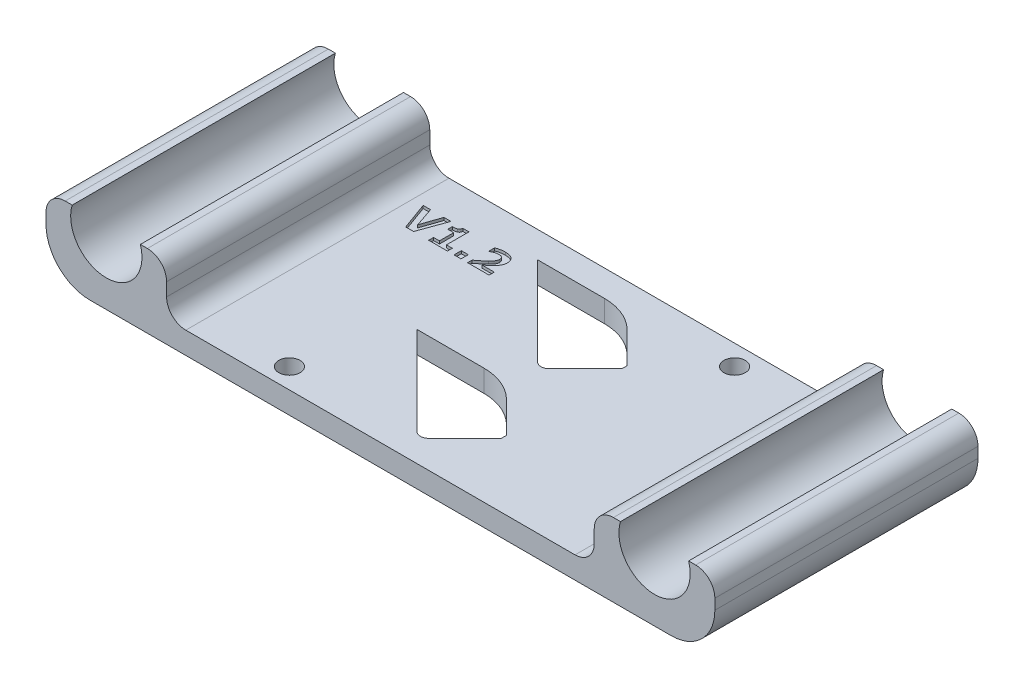
SolidWorks part; units mm, degrees
ref_plane "Front Plane" through (0, 0, 0) normal (0, 0, 1) x (1, 0, 0)
ref_plane "Top Plane" through (0, 0, 0) normal (0, 1, 0) x (1, 0, 0)
ref_plane "Right Plane" through (0, 0, 0) normal (1, 0, 0) x (0, 0, -1)
sketch "Sketch1" plane through (0, 0, 0) normal (0, 0, 1) x (1, 0, 0)
  line L0 (0, 13.4) -> (4.7839, 13.4)
  line L1 (0, 13.4) -> (0, 0)
  line L2 (122, 13.4) -> (122, 0)
  line L4 (117.2161, 13.4) -> (122, 13.4)
  line L5 (100, 13.4) -> (100, 4)
  line L6 (22, 4) -> (22, 13.4)
  line L7 (22, 4) -> (100, 4)
  line L8 (17.2161, 13.4) -> (22, 13.4)
  line L9 (11, 13.4) -> (11, 11.5) construction
  line L10 (11, 11.5) -> (111, 11.5) construction
  line L13 (100, 13.4) -> (104.7839, 13.4)
  line L18 (0, 0) -> (122, 0)
  arc A0 (104.7839, 13.4) -> (117.2161, 13.4) centre (111, 11.5) ccw
  arc A1 (4.7839, 13.4) -> (17.2161, 13.4) centre (11, 11.5) ccw
  dimension "D6" = 6.5
  dimension "D5" = 22
  dimension "D1" = 7.5
  dimension "D2" = 4
  dimension "D3" = 100
  dimension "D4" = 22
  dimension "D7" = 1.9
  dimension "D8" = 11
extrude "Boss-Extrude1" add sketch "Sketch1" along normal blind 48
fillet "Fillet1" radius 3.5 6 edges at (0, 13.4, 24) (22, 4, 24) (22, 13.4, 24) (100, 4, 24) (100, 13.4, 24) (122, 13.4, 24)
fillet "Fillet2" radius 8 2 edges at (122, 0, 24) (0, 0, 24)
ref_plane "Plane1" through (0, 0, 24) normal (0, 0, -1) x (-1, 0, 0)
ref_plane "Plane2" through (61, 0, 0) normal (-1, 0, 0) x (0, 0, 1)
sketch "Sketch6" plane through (0, 0, 0) normal (0, -1, 0) x (1, 0, 0)
  circle A0 centre (40.7, 44.3) radius 1.95
  circle A1 centre (81.3, 3.7) radius 1.95
  point P0 (40.7, 44.3)
  point P1 (81.3, 3.7)
  dimension "D1" = 3.9
extrude "Cut-Extrude2" cut sketch "Sketch6" against normal blind 6
sketch "Sketch7" plane through (0, 0, 0) normal (0, -1, 0) x (1, 0, 0)
  line L0 (63.6751, 44) -> (46.477, 26.8018)
  line L1 (71.3683, 36.3068) -> (63.6751, 44)
  line L2 (62.8027, 26.8018) -> (71.3683, 35.3675)
  line L3 (71.3683, 35.3675) -> (71.3683, 36.3068)
  line L4 (46.477, 26.8018) -> (62.8027, 26.8018)
  line L7 (8, 48) -> (114, 48) construction
  dimension "D1" = 45
  dimension "D2" = 45
  dimension "D3" = 90
  dimension "D4" = 4
extrude "Cut-Extrude3" cut sketch "Sketch7" against normal through all
pattern_linear "LPattern1" count 2 spacing 22 along (0, 0, -1) of "Cut-Extrude3"
fillet "Fillet3" radius 10 2 edges at (62.8027, 2, 26.8018) (62.8027, 2, 4.8018)
sketch "Sketch8" plane through (0, 0, 0) normal (1, 0, 0) x (0, 0, -1)
  line L5 (0, 0) -> (-48, 0) construction
  line L8 (-24, 0) -> (-24, -16.902) construction
  line L9 (-24, -22.0879) -> (-24, 22.0879) construction
  line L10 (-9.75, -0.25) -> (-13.5, -0.25)
  line L11 (-9.75, -3.05) -> (-13.5, -3.05)
  line L12 (-13.5, -5) -> (-8.9588, -5)
  line L13 (-13.5, -0.25) -> (-13.5, 0)
  line L14 (-13.5, 0) -> (-3, 0)
  line L15 (-13.5, -5) -> (-13.5, -3.05)
  line L16 (-3, 0) -> (-8.9588, -5)
  arc A1 (-9.75, -0.25) -> (-9.75, -3.05) centre (-9.75, -1.65) cw
  point P0 (0, 0)
  dimension "D4" = 3
  dimension "D1" = 1.4
  dimension "D2" = 0.25
  dimension "D3" = 40
  dimension "D5" = 3.75
  dimension "D6" = 5
  dimension "D7" = 10.5
extrude "Boss-Extrude2" add sketch "Sketch8" along normal blind 12 from offset 20
fillet "Fillet4" radius 3 2 edges at (26, -5, 8.9588) (26, 0, 3)
fillet "Fillet5" radius 0.5 2 edges at (26, -3.05, 13.5) (26, -5, 13.5)
pattern_linear "LPattern2" count 3 spacing 12 along (0, 0, 1) of "Boss-Extrude2", "Fillet4", "Fillet5"
sketch "Sketch9" plane through (0, 0, 0) normal (0, 0, -1) x (-1, 0, 0)
  line L0 (-32, 0) -> (-29.5, -5)
  line L1 (-8, 0) -> (-114, 0) construction
  line L2 (-29.5, -5) -> (-32, -5)
  line L3 (-32, -5) -> (-32, 0)
  line L4 (-20, 0) -> (-22.5, -5)
  line L5 (-22.5, -5) -> (-20, -5)
  line L6 (-20, -5) -> (-20, 0)
  line L7 (-20, -5) -> (-32, -5) construction
  line L8 (-20, -4.2981) -> (-20, -0.7019) construction
  line L9 (-32, -4.2981) -> (-32, -0.7019) construction
  dimension "D1" = 2.5
  dimension "D2" = 2.5
extrude "Cut-Extrude4" cut sketch "Sketch9" against normal through all
sketch "Sketch10" plane through (0, 4, 0) normal (0, 1, 0) x (1, 0, 0)
  text T0 "V1.2" font "Verdana" height 5
extrude "Cut-Extrude5" cut sketch "Sketch10" against normal blind 0.5
sketch "Sketch11" plane through (0, 0, 0) normal (0, -1, 0) x (1, 0, 0)
  line L1 (38.7, 40.3) -> (42.7, 40.3)
  line L2 (38.7, 40.3) -> (38.7, 5.3)
  line L3 (38.7, 5.3) -> (42.7, 5.3)
  line L4 (42.7, 40.3) -> (42.7, 5.3)
  line L5 (78.3, 4.7) -> (73.3, 4.7)
  line L6 (78.3, 4.7) -> (78.3, 22.7)
  line L7 (78.3, 22.7) -> (73.3, 22.7)
  line L8 (73.3, 4.7) -> (73.3, 22.7)
  line L9 (40.7, 40.3) -> (40.7, 44.3) construction
  point P12 (81.3, 3.7)
  dimension "D1" = 4
  dimension "D2" = 35
  dimension "D3" = 4
  dimension "D4" = 1
  dimension "D5" = 18
  dimension "D6" = 8
  dimension "D7" = 5
extrude "Cut-Extrude6" cut sketch "Sketch11" against normal blind 2.5
chamfer "Chamfer1" distance 1.5 angle 45 8 edges at (75.8, 0, 4.7) (78.3, 0, 13.7) (73.3, 0, 13.7) (75.8, 0, 22.7) (40.7, 0, 5.3) (42.7, 0, 22.8) (38.7, 0, 22.8) (40.7, 0, 40.3)
fillet "Fillet6" radius 1.5 2 edges at (63.6751, 2, 22) (63.6751, 2, 44)
sketch "Sketch12" plane through (0, 0, 0) normal (1, 0, 0) x (0, 0, -1)
  line L0 (-11, 0) -> (-13.5173, -3)
  line L1 (-1.9081, 0) -> (-13.5, 0) construction
  line L2 (-13.5173, -3) -> (-15.5173, -3)
  line L3 (-15.5173, -3) -> (-15.5173, 0)
  line L4 (0, 0) -> (-48, 0) construction
  line L5 (-15.5173, 0) -> (-11, 0)
  dimension "D1" = 50
  dimension "D2" = 11
  dimension "D3" = 2
  dimension "D4" = 3
extrude "Boss-Extrude3" add sketch "Sketch12" along normal blind 4 from offset 15
fillet "Fillet7" radius 1 2 edges at (15, -1.5, 12.2586) (19, -1.5, 12.2586)
fillet "Fillet8" radius 1 1 edges at (17, -3, 15.5173)
fillet "Fillet9" radius 1 5 edges at (19, 0, 13.9114) (18.7071, 0, 11.3823) (17, 0, 11) (15.2929, 0, 11.3823) (15, 0, 13.9114)
pattern_linear "LPattern3" count 3 spacing 12 along (0, 0, 1) of "Fillet9", "Boss-Extrude3", "Fillet8", "Fillet7"
